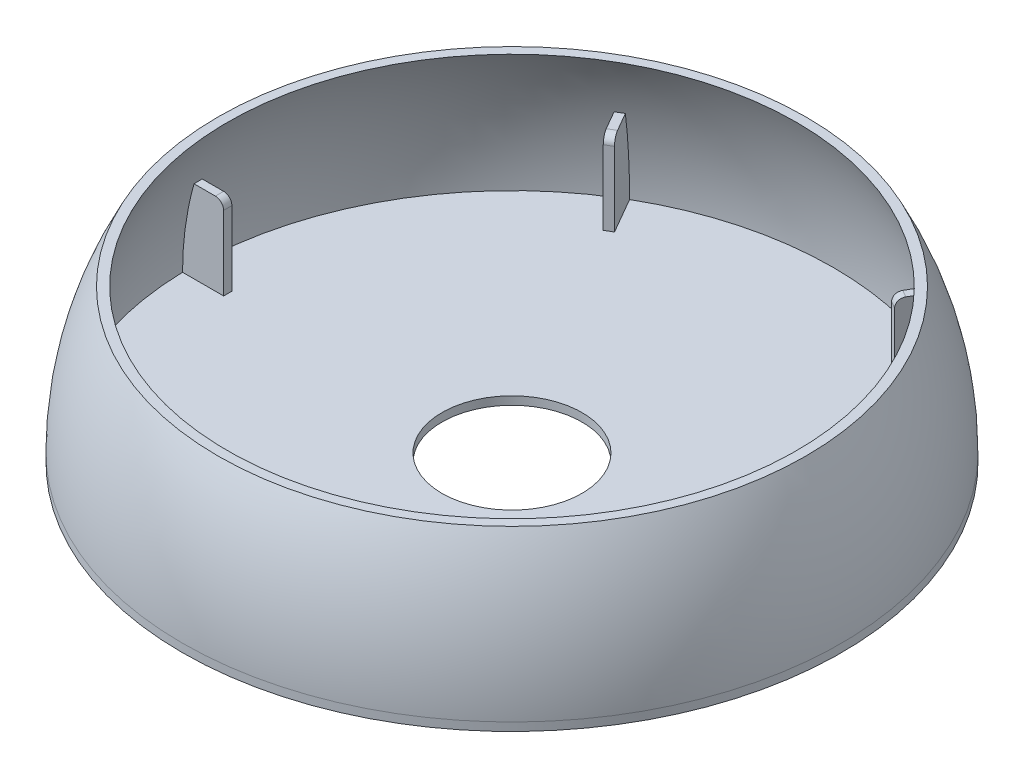
SolidWorks part; units mm, degrees
ref_plane "Front Plane" through (0, 0, 0) normal (0, 0, 1) x (1, 0, 0)
ref_plane "Top Plane" through (0, 0, 0) normal (0, 1, 0) x (1, 0, 0)
ref_plane "Right Plane" through (0, 0, 0) normal (1, 0, 0) x (0, 0, -1)
sketch "Sketch1" plane through (0, 0, 0) normal (0, 1, 0) x (1, 0, 0)
  circle A0 centre (0, 0) radius 80
  circle A2 centre (0, 0) radius 17
  dimension "D1" = 160
  dimension "D2" = 34
extrude "Boss-Extrude1" add sketch "Sketch1" along normal blind 2
sketch "Sketch3" plane through (0, 0, 0) normal (0, 0, 1) x (1, 0, 0)
  line L0 (-80, 0) -> (-80, 2)
  line L1 (-80, 2) -> (-78, 2)
  line L2 (-69.0625, 37) -> (-71.3325, 37)
  line L3 (0, 0) -> (0, 18.9646) construction
  arc A0 (-80, 2) -> (-71.3325, 37) centre (-5, 2) cw
  arc A2 (-78, 2) -> (-69.0625, 37) centre (-5, 2) cw
  arc A3 (-78, 2) -> (-69.5636, 36.0667) centre (-5, 2) cw construction
  dimension "D1" = 75
  dimension "D4" = 2
  dimension "D2" = 35
  dimension "D3" = 2
revolve "Revolve2" add sketch "Sketch3" angle 360 about L3 region at (-76.0419, 19.8629, 0)
sketch "Sketch5" plane through (0, 0, 0) normal (0, 0, 1) x (1, 0, 0)
  line L0 (78, 2) -> (-78, 2) construction
  line L1 (-68, 2) -> (-78, 2)
  line L2 (-75.2068, 22) -> (-70, 22)
  line L3 (-68, 20) -> (-68, 2)
  arc A0 (-69.0625, 37) -> (-78, 2) centre (-5, 2) ccw construction
  arc A1 (-75.2068, 22) -> (-78, 2) centre (-5, 2) ccw
  arc A2 (-70, 22) -> (-68, 20) centre (-70, 20) cw
  dimension "D1" = 2
  dimension "D2" = 20
  dimension "D3" = 10
extrude "Boss-Extrude2" add sketch "Sketch5" along normal blind 2
pattern_circular "CirPattern1" count 6 over 360 about axis through (0, 0, 0) along (0, 1, 0) of "Boss-Extrude2" reverse direction yes
sketch "Sketch6" plane through (0, 0, 0) normal (0, -1, 0) x (1, 0, 0)
  line L1 (-0.75, 68) -> (0.75, 68)
  line L2 (-0.75, 68) -> (-0.75, 59)
  line L3 (-0.75, 59) -> (0.75, 59)
  line L4 (0.75, 68) -> (0.75, 59)
  line L5 (-0.75, 68) -> (0.75, 59) construction
  line L6 (-0.75, 59) -> (0.75, 68) construction
  point P0 (0, 63.5)
  dimension "D1" = 9
  dimension "D2" = 1.5
  dimension "D3" = 59
extrude "Cut-Extrude1" cut sketch "Sketch6" against normal blind 1 draft 30
pattern_circular "CirPattern2" count 100 over 360 about axis through (0, 0, 0) along (0, 1, 0) of "Cut-Extrude1"
